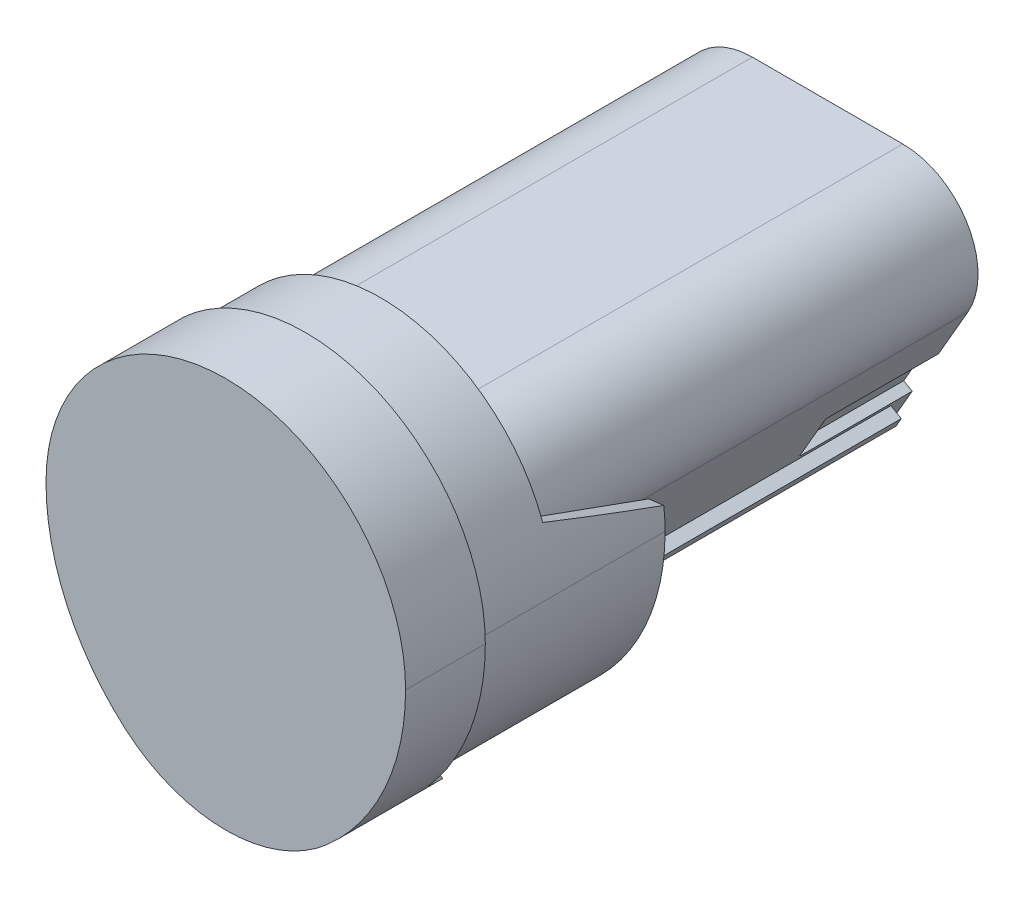
SolidWorks part; units mm, degrees
ref_plane "Plan de face" through (0, 0, 0) normal (0, 0, 1) x (1, 0, 0)
ref_plane "Plan de dessus" through (0, 0, 0) normal (0, 1, 0) x (1, 0, 0)
ref_plane "Plan de droite" through (0, 0, 0) normal (1, 0, 0) x (0, 0, -1)
ref_axis "Axe1" through (0, 0, 84) along (0, 0, -1)
sketch "Esquisse1" plane through (0, 0, 0) normal (0, 0, 1) x (1, 0, 0)
  line L0 (-10, 15.7735) -> (10, 15.7735)
  line L1 (-18.6603, 0.7735) -> (-8.6603, -16.547)
  line L2 (8.6603, -16.547) -> (18.6603, 0.7735)
  line L3 (-13.6603, -7.8868) -> (18.6603, 10.7735) construction
  line L4 (13.6603, -7.8868) -> (-18.6603, 10.7735) construction
  line L5 (0, -21.547) -> (0, 15.7735) construction
  line L6 (-20, 2.0501) -> (-20, 16.2695) construction
  line L7 (20, 1.5053) -> (20, 13.4658) construction
  line L8 (445.3732, -108.8997) -> (521.6093, -834.2377) construction
  line L9 (-7.7491, -6.7833) -> (-9.7491, -3.3192) construction
  line L10 (-7.7491, -6.7833) -> (-6.6232, -6.1333) construction
  line L11 (-9.7491, -3.3192) -> (-8.6232, -2.6692) construction
  line L12 (-6.6232, -6.1333) -> (-8.6232, -2.6692) construction
  line L13 (-7.7491, -6.7833) -> (-8.6232, -2.6692) construction
  line L14 (-9.7491, -3.3192) -> (-6.6232, -6.1333) construction
  arc A0 (-8.6603, -16.547) -> (8.6603, -16.547) centre (0, -11.547) ccw
  arc A1 (10, 15.7735) -> (18.6603, 0.7735) centre (10, 5.7735) cw
  arc A2 (-10, 15.7735) -> (-18.6603, 0.7735) centre (-10, 5.7735) ccw
  circle A3 centre (-9.3904, 5.4216) radius 2.9644 construction
  point P15 (0, 0)
  point P26 (-8.1861, -4.7263)
  dimension "D1" = 10
  dimension "D2" = 40
  dimension "D3" = 1.3
  dimension "D4" = 4
extrude "Boss.-Extru.1" add sketch "Esquisse1" along normal blind 80
sketch "Esquisse2" plane through (0, 0, 80) normal (0, 0, 1) x (1, 0, 0)
  line L0 (-12681.8859, 1278.2104) -> (-12646.9605, 1282.3837) construction
  line L1 (-242.0525, 250.143) -> (-212.0525, 250.143) construction
  line L2 (30.4051, 69.3804) -> (25.1957, 98.9247) construction
  line L3 (0, -28.2265) -> (0, 23.7735) construction
  line L4 (-7.624, 23.7735) -> (-13.8216, 23.7735) construction
  line L5 (-9.437, -28.2265) -> (-46.2994, -28.2265) construction
  line L6 (-23.9, 23.7735) -> (-23.9, -28.2265) construction
  line L7 (0, 23.7735) -> (0, -28.2265)
  line L9 (0, -28.2265) -> (0, -21.547) construction
  line L10 (0, 23.7735) -> (0, 15.7735) construction
  arc A4 (-8.6603, -16.547) -> (8.6603, -16.547) centre (0, -11.547) ccw construction
  arc A5 (0, 23.7735) -> (-23.9, -0.1265) centre (0, -0.1265) ccw
  arc A6 (-23.9, -0.1265) -> (-13.3729, -23.2265) centre (6.7081, -0.1265) ccw
  arc A7 (-13.3729, -23.2265) -> (0, -28.2265) centre (0, -7.8431) ccw
  dimension "D3" = 23.9
  dimension "D5" = 8
  dimension "D6" = 5
  dimension "D1" = 35.1738
  dimension "D2" = 30
  dimension "D4" = 52
extrude "Boss.-Extru.2" add sketch "Esquisse2" against normal blind 10.6
mirror "Symétrie1" about plane through (0, 0, 0) normal (1, 0, 0) of "Boss.-Extru.2"
sketch "Esquisse4" plane through (0, 0, 69.4) normal (0, 0, -1) x (-1, 0, 0)
  arc A8 (-22.9, -0.1265) -> (-12.7168, -22.4718) centre (6.7081, -0.1265) ccw
  arc A10 (-12.7168, -22.4718) -> (12.7168, -22.4718) centre (0, -7.8431) ccw
  arc A11 (-12.7168, -22.4718) -> (12.7168, -22.4718) centre (0, -7.8431) ccw
  arc A16 (-22.9, -0.1265) -> (-12.7168, -22.4718) centre (6.7081, -0.1265) ccw
  arc A17 (12.7168, -22.4718) -> (22.9, -0.1265) centre (-6.7081, -0.1265) ccw
  arc A18 (12.7168, -22.4718) -> (22.9, -0.1265) centre (-6.7081, -0.1265) ccw
  arc A19 (22.9, -0.1265) -> (-22.9, -0.1265) centre (0, -0.1265) ccw
  arc A20 (22.9, -0.1265) -> (-22.9, -0.1265) centre (0, -0.1265) ccw
  dimension "D1" = 1
extrude "Boss.-Extru.3" add sketch "Esquisse4" along normal blind 10
sketch "Esquisse6" plane through (0, 0, 69.4) normal (0, 0, -1) x (-1, 0, 0)
  line L0 (0, -28.2265) -> (0, 23.7735) construction
  line L1 (14.75, -21.9532) -> (0, -13.4765)
  line L2 (0, -13.4765) -> (0, -28.2265)
  arc A0 (0, -28.2265) -> (13.3729, -23.2265) centre (0, -7.8431) ccw
  arc A1 (0, -28.2265) -> (13.3729, -23.2265) centre (0, -7.8431) ccw construction
  arc A2 (13.3729, -23.2265) -> (23.9, -0.1265) centre (-6.7081, -0.1265) ccw construction
  arc A3 (13.3729, -23.2265) -> (14.75, -21.9532) centre (-6.7081, -0.1265) ccw
  dimension "D1" = 14.75
  dimension "D2" = 14.75
extrude "Boss.-Extru.4" add sketch "Esquisse6" along normal blind 3.5
mirror "Symétrie2" about plane through (0, 0, 0) normal (1, 0, 0) of "Boss.-Extru.4"
chamfer "Chanfrein1" distance 2 distance2 3.5 2 edges at (-14.2993, -21.6942, 69.4) (14.2993, -21.6942, 69.4) first distance on face at (0, -5.5207, 69.4)
sketch "Esquisse7" plane through (0, 0, 59.4) normal (0, 0, -1) x (-1, 0, 0)
  line L0 (0, -27.2265) -> (0, 0) construction
  line L2 (10, 15.7735) -> (-10, 15.7735) construction
  line L3 (0, -27.2265) -> (0, 0)
  line L4 (0, 0) -> (22.7156, 2.7735)
  arc A0 (-12.7168, -22.4718) -> (12.7168, -22.4718) centre (0, -7.8431) ccw construction
  arc A1 (0, -27.2265) -> (12.7168, -22.4718) centre (0, -7.8431) ccw
  arc A2 (-12.7168, -22.4718) -> (12.7168, -22.4718) centre (0, -7.8431) ccw construction
  arc A3 (12.7168, -22.4718) -> (22.9, -0.1265) centre (-6.7081, -0.1265) ccw
  arc A4 (12.7168, -22.4718) -> (22.9, -0.1265) centre (-6.7081, -0.1265) ccw construction
  arc A5 (22.9, -0.1265) -> (22.7156, 2.7735) centre (0, -0.1265) ccw
  arc A6 (22.9, -0.1265) -> (-22.9, -0.1265) centre (0, -0.1265) ccw construction
  arc A7 (22.9, -0.1265) -> (-22.9, -0.1265) centre (0, -0.1265) ccw construction
  dimension "D1" = 13
extrude "Boss.-Extru.5" add sketch "Esquisse7" along normal blind 14.9
mirror "Symétrie4" about plane through (0, 0, 0) normal (1, 0, 0) of "Boss.-Extru.5"
chamfer "Chanfrein2" distance 5 distance2 14.9 2 edges at (-21.0591, 2.5712, 59.4) (21.0591, 2.5712, 59.4) first distance on face at (0, 11.1203, 59.4)
sketch "Esquisse8" plane through (0, 0, 0) normal (0, 0, -1) x (-1, 0, 0)
  line L0 (-18.6603, 0.7735) -> (-8.6603, -16.547) construction
  line L1 (18.6603, 0.7735) -> (8.6603, -16.547) construction
  line L2 (-10, 15.7735) -> (10, 15.7735) construction
  line L3 (-18.6603, 0.7735) -> (-8.6603, -16.547)
  line L4 (18.6603, 0.7735) -> (8.6603, -16.547)
  line L5 (-10, 15.7735) -> (10, 15.7735)
  line L6 (-20.7317, 2.5202) -> (-20.1083, 7.1382)
  line L7 (-16.0835, 13.9607) -> (-12.4653, 16.6493)
  line L8 (20.7317, 2.5202) -> (20.1083, 7.1382)
  line L9 (12.4653, 16.6493) -> (16.0835, 13.9607)
  arc A0 (-10, 15.7735) -> (-18.6603, 0.7735) centre (-10, 5.7735) ccw construction
  arc A1 (-8.6603, -16.547) -> (8.6603, -16.547) centre (0, -11.547) ccw construction
  arc A2 (18.6603, 0.7735) -> (10, 15.7735) centre (10, 5.7735) ccw construction
  arc A3 (-10, 15.7735) -> (-18.6603, 0.7735) centre (-10, 5.7735) ccw
  arc A4 (-8.6603, -16.547) -> (8.6603, -16.547) centre (0, -11.547) ccw
  arc A5 (18.6603, 0.7735) -> (10, 15.7735) centre (10, 5.7735) ccw
  arc A6 (16.0835, 13.9607) -> (20.1083, 7.1382) centre (10, 5.7735) cw
  arc A42 (-12.4653, 16.6493) -> (12.4653, 16.6493) centre (0, -0.1265) cw
  arc A43 (-10, 15.9735) -> (-18.8335, 0.6735) centre (-10, 5.7735) ccw construction
  arc A44 (18.8335, 0.6735) -> (10, 15.9735) centre (10, 5.7735) ccw construction
  arc A45 (-20.1083, 7.1382) -> (-16.0835, 13.9607) centre (-10, 5.7735) cw
  arc A50 (20.7317, 2.5202) -> (19.6527, 6.9857) centre (0, -0.1265) ccw
  arc A51 (20.9, -0.1265) -> (20.7317, 2.5202) centre (0, -0.1265) ccw
  arc A52 (11.4047, -20.9624) -> (20.9, -0.1265) centre (-6.7081, -0.1265) ccw
  arc A53 (-11.4047, -20.9624) -> (11.4047, -20.9624) centre (0, -7.8431) ccw
  arc A54 (-20.9, -0.1265) -> (-11.4047, -20.9624) centre (6.7081, -0.1265) ccw
  arc A55 (-20.7317, 2.5202) -> (-20.9, -0.1265) centre (0, -0.1265) ccw
  arc A56 (-19.6527, 6.9857) -> (-20.7317, 2.5202) centre (0, -0.1265) ccw
  arc A57 (19.6527, 6.9857) -> (-19.6527, 6.9857) centre (0, -0.1265) ccw
  arc A58 (20.7317, 2.5202) -> (19.6527, 6.9857) centre (0, -0.1265) ccw construction
  arc A59 (20.9, -0.1265) -> (20.7317, 2.5202) centre (0, -0.1265) ccw
  arc A60 (11.4047, -20.9624) -> (20.9, -0.1265) centre (-6.7081, -0.1265) ccw
  arc A61 (-11.4047, -20.9624) -> (11.4047, -20.9624) centre (0, -7.8431) ccw
  arc A62 (-20.9, -0.1265) -> (-11.4047, -20.9624) centre (6.7081, -0.1265) ccw
  arc A63 (-20.7317, 2.5202) -> (-20.9, -0.1265) centre (0, -0.1265) ccw
  arc A64 (-19.6527, 6.9857) -> (-20.7317, 2.5202) centre (0, -0.1265) ccw construction
  arc A65 (19.6527, 6.9857) -> (-19.6527, 6.9857) centre (0, -0.1265) ccw construction
  dimension "D2" = 0.2
  dimension "D1" = 2
extrude "Enlèv. mat.-Extru.1" cut sketch "Esquisse8" against normal offset from surface (61.9 mm away) 2.5 up to face at (0, 13.4185, 59.4) offset beyond the face yes
sketch "Esquisse9" plane through (0, 0, 0) normal (0, 0, -1) x (-1, 0, 0)
  line L0 (-10.2144, -13.8552) -> (-11.6, -14.6552)
  line L1 (-8.6603, -16.547) -> (-18.6603, 0.7735) construction
  line L2 (-11.6, -14.6552) -> (-12.3, -13.4428)
  line L3 (-12.3, -13.4428) -> (-10.9144, -12.6428)
  line L4 (-10.9144, -12.6428) -> (-10.2144, -13.8552)
  line L5 (0, 28.6) -> (0, -28.6) construction
  line L6 (10.9144, -12.6428) -> (10.2144, -13.8552)
  line L7 (12.3, -13.4428) -> (10.9144, -12.6428)
  line L8 (11.6, -14.6552) -> (12.3, -13.4428)
  line L9 (10.2144, -13.8552) -> (11.6, -14.6552)
  dimension "D1" = 1.6
  dimension "D2" = 1.4
  dimension "D3" = 24.6
extrude "Boss.-Extru.8" add sketch "Esquisse9" against normal up to next from offset 2.5 offset against normal yes
sketch "Esquisse10" plane through (0, 0, 0) normal (0, 0, -1) x (-1, 0, 0)
  line L0 (-11.25, -12.0614) -> (-10.1242, -11.4114)
  line L1 (-10.9144, -12.6428) -> (-18.6603, 0.7735) construction
  line L2 (-10.1242, -11.4114) -> (-13.6242, -5.3493)
  line L3 (-13.6242, -5.3493) -> (-14.75, -5.9993)
  line L4 (-8.6603, -16.547) -> (-18.6603, 0.7735) construction
  line L5 (-14.75, -5.9993) -> (-11.25, -12.0614)
  line L6 (11.25, -12.0614) -> (14.75, -5.9993)
  line L7 (18.6603, 0.7735) -> (10.9144, -12.6428) construction
  line L8 (18.6603, 0.7735) -> (8.6603, -16.547) construction
  line L9 (14.75, -5.9993) -> (13.6242, -5.3493)
  line L10 (13.6242, -5.3493) -> (10.1242, -11.4114)
  line L11 (10.1242, -11.4114) -> (11.25, -12.0614)
  point P14 (0, 0)
  point P17 (0, 0)
  dimension "D1" = 1.3
  dimension "D2" = 7
  dimension "D3" = 22.5
  dimension "D4" = 1.3
extrude "Enlèv. mat.-Extru.4" cut sketch "Esquisse10" against normal blind 15 contours L2 L3 L5 L0 | L11 L6 L9 L10
